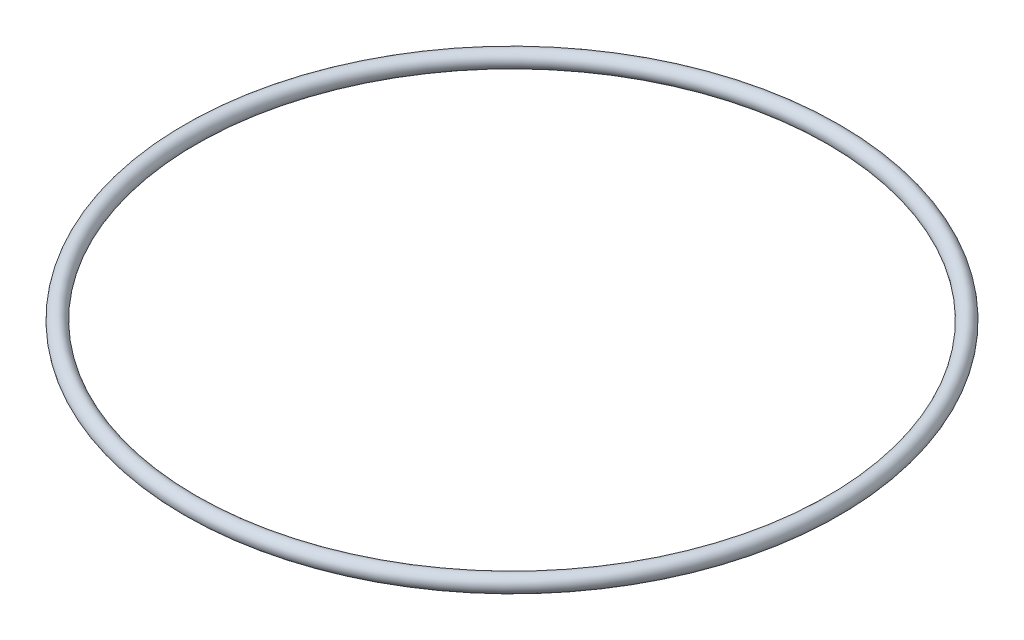
SolidWorks part; units mm, degrees
ref_plane "Plan de face" through (0, 0, 0) normal (0, 0, 1) x (1, 0, 0)
ref_plane "Plan de dessus" through (0, 0, 0) normal (0, 1, 0) x (1, 0, 0)
ref_plane "Plan de droite" through (0, 0, 0) normal (1, 0, 0) x (0, 0, -1)
sketch "Esquisse1" plane through (0, 0, 0) normal (0, 0, 1) x (1, 0, 0)
  line L0 (0, 0) -> (0, 7.567) construction
  line L1 (0, 0) -> (-20, 0) construction
  circle A0 centre (-20, 0) radius 0.5
  dimension "D1" = 1
  dimension "D2" = 40
revolve "Révolution1" add sketch "Esquisse1" angle 360 about L0
